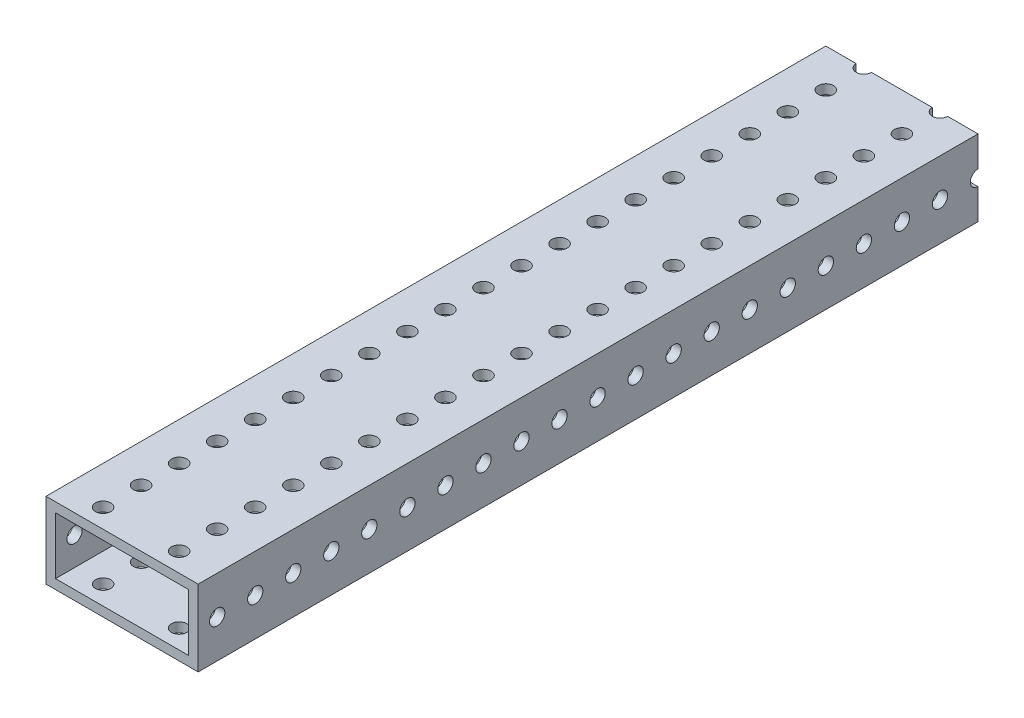
SolidWorks part; units mm, degrees
material "6061-T6 (SS)"
ref_plane "Front Plane" through (0, 0, 0) normal (0, 0, 1) x (1, 0, 0)
ref_plane "Top Plane" through (0, 0, 0) normal (0, 1, 0) x (1, 0, 0)
ref_plane "Right Plane" through (0, 0, 0) normal (1, 0, 0) x (0, 0, -1)
sketch "Sketch1" plane through (0, 0, 0) normal (0, 0, 1) x (1, 0, 0)
  line L0 (-22.225, 9.525) -> (22.225, 9.525)
  line L1 (-25.4, 12.7) -> (25.4, 12.7)
  line L2 (-25.4, 12.7) -> (-25.4, -12.7)
  line L3 (-25.4, -12.7) -> (25.4, -12.7)
  line L4 (25.4, 12.7) -> (25.4, -12.7)
  line L5 (22.225, 9.525) -> (22.225, -9.525)
  line L6 (-22.225, -9.525) -> (22.225, -9.525)
  line L7 (-22.225, 9.525) -> (-22.225, -9.525)
  line L8 (-25.4, 12.7) -> (25.4, -12.7) construction
  line L9 (25.4, 12.7) -> (-25.4, -12.7) construction
  point P5 (0, 0)
  dimension "D1" = 50.8
  dimension "D2" = 25.4
  dimension "D3" = 3.175
extrude "Boss-Extrude1" add sketch "Sketch1" along normal mid plane 368.3
sketch "Sketch5" plane through (-25.4, 0, 0) normal (-1, 0, 0) x (0, 0, 1)
  line L0 (184.15, -12.7) -> (-184.15, -12.7) construction
  line L1 (-184.15, 12.7) -> (-120.65, 12.7)
  line L2 (-184.15, 12.7) -> (-184.15, -12.7)
  line L3 (-184.15, -12.7) -> (-120.65, -12.7)
  line L4 (-120.65, 12.7) -> (-120.65, -12.7)
  dimension "D1" = 63.5
sketch "Sketch6" plane through (25.4, 0, 0) normal (1, 0, 0) x (0, 0, -1)
  line L0 (-184.15, -12.7) -> (-184.15, 12.7) construction
  line L1 (-184.15, 12.7) -> (184.15, 12.7) construction
  circle A0 centre (-177.8, 0) radius 2.5527
  circle A1 centre (-165.1, 0) radius 2.5527
  circle A2 centre (-152.4, 0) radius 2.5527
  circle A3 centre (-139.7, 0) radius 2.5527
  circle A4 centre (-127, 0) radius 2.5527
  circle A5 centre (-114.3, 0) radius 2.5527
  circle A6 centre (-101.6, 0) radius 2.5527
  circle A7 centre (-88.9, 0) radius 2.5527
  circle A8 centre (-76.2, 0) radius 2.5527
  circle A9 centre (-63.5, 0) radius 2.5527
  circle A10 centre (-50.8, 0) radius 2.5527
  circle A11 centre (-38.1, 0) radius 2.5527
  circle A12 centre (-25.4, 0) radius 2.5527
  circle A13 centre (-12.7, 0) radius 2.5527
  circle A14 centre (0, 0) radius 2.5527
  circle A15 centre (12.7, 0) radius 2.5527
  circle A16 centre (25.4, 0) radius 2.5527
  circle A17 centre (38.1, 0) radius 2.5527
  circle A18 centre (50.8, 0) radius 2.5527
  circle A19 centre (63.5, 0) radius 2.5527
  circle A20 centre (76.2, 0) radius 2.5527
  circle A21 centre (88.9, 0) radius 2.5527
  circle A22 centre (101.6, 0) radius 2.5527
  circle A23 centre (114.3, 0) radius 2.5527
  circle A24 centre (127, 0) radius 2.5527 construction
  circle A25 centre (139.7, 0) radius 2.5527 construction
  circle A26 centre (152.4, 0) radius 2.5527 construction
  circle A27 centre (165.1, 0) radius 2.5527 construction
  circle A28 centre (177.8, 0) radius 2.5527 construction
  dimension "D1" = 6.35
  dimension "D2" = 12.7
  dimension "D3" = 5.1054
  dimension "D4" = 29
extrude "Cut-Extrude5" cut sketch "Sketch6" against normal through all
extrude "Cut-Extrude6" cut sketch "Sketch5" against normal through all
sketch "Sketch2" plane through (0, 12.7, 0) normal (0, 1, 0) x (1, 0, 0)
  line L0 (25.4, -184.15) -> (-25.4, -184.15) construction
  line L1 (-25.4, -184.15) -> (-25.4, 120.65) construction
  line L4 (25.4, 184.15) -> (-25.4, 184.15) construction
  circle A0 centre (12.7, -177.8) radius 2.5527
  circle A1 centre (25.4, -171.45) radius 2.5527 construction
  circle A2 centre (-12.7, -177.8) radius 2.5527
  circle A3 centre (-12.7, -165.1) radius 2.5527
  circle A4 centre (12.7, -165.1) radius 2.5527 construction
  circle A5 centre (25.4, -158.75) radius 2.5527 construction
  circle A6 centre (-12.7, -152.4) radius 2.5527
  circle A7 centre (12.7, -152.4) radius 2.5527 construction
  circle A8 centre (25.4, -146.05) radius 2.5527 construction
  circle A9 centre (-12.7, -139.7) radius 2.5527
  circle A10 centre (12.7, -139.7) radius 2.5527 construction
  circle A11 centre (25.4, -133.35) radius 2.5527 construction
  circle A12 centre (-12.7, -127) radius 2.5527
  circle A13 centre (12.7, -127) radius 2.5527 construction
  circle A14 centre (25.4, -120.65) radius 2.5527 construction
  circle A15 centre (-12.7, -114.3) radius 2.5527
  circle A16 centre (12.7, -114.3) radius 2.5527 construction
  circle A17 centre (25.4, -107.95) radius 2.5527 construction
  circle A18 centre (-12.7, -101.6) radius 2.5527
  circle A19 centre (12.7, -101.6) radius 2.5527 construction
  circle A20 centre (25.4, -95.25) radius 2.5527 construction
  circle A21 centre (-12.7, -88.9) radius 2.5527
  circle A22 centre (12.7, -88.9) radius 2.5527 construction
  circle A23 centre (25.4, -82.55) radius 2.5527 construction
  circle A24 centre (-12.7, -76.2) radius 2.5527
  circle A25 centre (12.7, -76.2) radius 2.5527 construction
  circle A26 centre (25.4, -69.85) radius 2.5527 construction
  circle A27 centre (-12.7, -63.5) radius 2.5527
  circle A28 centre (12.7, -63.5) radius 2.5527 construction
  circle A29 centre (25.4, -57.15) radius 2.5527 construction
  circle A30 centre (-12.7, -50.8) radius 2.5527
  circle A31 centre (12.7, -50.8) radius 2.5527 construction
  circle A32 centre (25.4, -44.45) radius 2.5527 construction
  circle A33 centre (-12.7, -38.1) radius 2.5527
  circle A34 centre (12.7, -38.1) radius 2.5527 construction
  circle A35 centre (25.4, -31.75) radius 2.5527 construction
  circle A36 centre (-12.7, -25.4) radius 2.5527
  circle A37 centre (12.7, -25.4) radius 2.5527 construction
  circle A38 centre (25.4, -19.05) radius 2.5527 construction
  circle A39 centre (-12.7, -12.7) radius 2.5527
  circle A40 centre (12.7, -12.7) radius 2.5527 construction
  circle A41 centre (25.4, -6.35) radius 2.5527 construction
  circle A42 centre (-12.7, 0) radius 2.5527
  circle A43 centre (12.7, 0) radius 2.5527 construction
  circle A44 centre (25.4, 6.35) radius 2.5527 construction
  circle A45 centre (-12.7, 12.7) radius 2.5527
  circle A46 centre (12.7, 12.7) radius 2.5527 construction
  circle A47 centre (25.4, 19.05) radius 2.5527 construction
  circle A48 centre (-12.7, 25.4) radius 2.5527
  circle A49 centre (12.7, 25.4) radius 2.5527 construction
  circle A50 centre (25.4, 31.75) radius 2.5527 construction
  circle A51 centre (-12.7, 38.1) radius 2.5527
  circle A52 centre (12.7, 38.1) radius 2.5527 construction
  circle A53 centre (25.4, 44.45) radius 2.5527 construction
  circle A54 centre (-12.7, 50.8) radius 2.5527
  circle A55 centre (12.7, 50.8) radius 2.5527 construction
  circle A56 centre (25.4, 57.15) radius 2.5527 construction
  circle A57 centre (-12.7, 63.5) radius 2.5527
  circle A58 centre (12.7, 63.5) radius 2.5527 construction
  circle A59 centre (25.4, 69.85) radius 2.5527 construction
  circle A60 centre (-12.7, 76.2) radius 2.5527
  circle A61 centre (12.7, 76.2) radius 2.5527 construction
  circle A62 centre (25.4, 82.55) radius 2.5527 construction
  circle A63 centre (-12.7, 88.9) radius 2.5527
  circle A64 centre (12.7, 88.9) radius 2.5527 construction
  circle A65 centre (25.4, 95.25) radius 2.5527 construction
  circle A66 centre (-12.7, 101.6) radius 2.5527
  circle A67 centre (12.7, 101.6) radius 2.5527 construction
  circle A68 centre (25.4, 107.95) radius 2.5527 construction
  circle A69 centre (-12.7, 114.3) radius 2.5527 construction
  circle A70 centre (12.7, 114.3) radius 2.5527 construction
  circle A71 centre (25.4, 120.65) radius 2.5527 construction
  circle A72 centre (-12.7, 127) radius 2.5527 construction
  circle A73 centre (12.7, 127) radius 2.5527 construction
  circle A74 centre (25.4, 133.35) radius 2.5527 construction
  circle A75 centre (-12.7, 139.7) radius 2.5527
  circle A76 centre (12.7, 139.7) radius 2.5527 construction
  circle A77 centre (25.4, 146.05) radius 2.5527 construction
  circle A78 centre (-12.7, 152.4) radius 2.5527
  circle A79 centre (12.7, 152.4) radius 2.5527 construction
  circle A80 centre (25.4, 158.75) radius 2.5527 construction
  circle A81 centre (-12.7, 165.1) radius 2.5527
  circle A82 centre (12.7, 165.1) radius 2.5527 construction
  circle A83 centre (25.4, 171.45) radius 2.5527 construction
  circle A84 centre (-12.7, 177.8) radius 2.5527 construction
  circle A85 centre (12.7, 177.8) radius 2.5527 construction
  circle A86 centre (25.4, 184.15) radius 2.5527 construction
  circle A87 centre (-12.7, 190.5) radius 2.5527
  circle A88 centre (12.7, 190.5) radius 2.5527 construction
  circle A89 centre (25.4, 196.85) radius 2.5527 construction
  circle A90 centre (-12.7, 203.2) radius 2.5527
  circle A91 centre (12.7, 203.2) radius 2.5527 construction
  circle A92 centre (25.4, 209.55) radius 2.5527 construction
  circle A93 centre (-12.7, 215.9) radius 2.5527
  circle A94 centre (12.7, 215.9) radius 2.5527 construction
  circle A95 centre (25.4, 222.25) radius 2.5527 construction
  circle A96 centre (-12.7, 228.6) radius 2.5527
  circle A97 centre (12.7, 228.6) radius 2.5527 construction
  circle A98 centre (25.4, 234.95) radius 2.5527 construction
  circle A99 centre (-12.7, 241.3) radius 2.5527
  circle A100 centre (12.7, 241.3) radius 2.5527 construction
  circle A101 centre (25.4, 247.65) radius 2.5527 construction
  circle A108 centre (-12.7, 266.7) radius 2.5527 [skipped]
  circle A109 centre (12.7, 266.7) radius 2.5527 [skipped]
  circle A110 centre (25.4, 273.05) radius 2.5527 [skipped]
  circle A111 centre (-12.7, 254) radius 2.5527 [skipped]
  circle A112 centre (12.7, 254) radius 2.5527 [skipped]
  circle A113 centre (25.4, 260.35) radius 2.5527 [skipped]
  circle A114 centre (25.4, 260.35) radius 2.5527 construction
  circle A115 centre (12.7, 254) radius 2.5527 construction
  circle A116 centre (-12.7, 254) radius 2.5527
  circle A117 centre (25.4, 273.05) radius 2.5527 construction
  circle A118 centre (12.7, 266.7) radius 2.5527 construction
  circle A119 centre (-12.7, 266.7) radius 2.5527
  circle A120 centre (25.4, 285.75) radius 2.5527 construction
  circle A121 centre (12.7, 279.4) radius 2.5527 construction
  circle A122 centre (-12.7, 279.4) radius 2.5527
  circle A123 centre (25.4, 298.45) radius 2.5527 construction
  circle A124 centre (12.7, 292.1) radius 2.5527 construction
  circle A125 centre (-12.7, 292.1) radius 2.5527
  circle A126 centre (25.4, 311.15) radius 2.5527 construction
  circle A127 centre (12.7, 304.8) radius 2.5527 construction
  circle A128 centre (-12.7, 304.8) radius 2.5527
  circle A129 centre (25.4, 323.85) radius 2.5527 construction
  circle A130 centre (12.7, 317.5) radius 2.5527 construction
  circle A131 centre (-12.7, 317.5) radius 2.5527
  circle A132 centre (25.4, 336.55) radius 2.5527 construction
  circle A133 centre (12.7, 330.2) radius 2.5527 construction
  circle A134 centre (-12.7, 330.2) radius 2.5527
  circle A135 centre (25.4, 349.25) radius 2.5527 construction
  circle A136 centre (12.7, 342.9) radius 2.5527 construction
  circle A137 centre (-12.7, 342.9) radius 2.5527
  circle A138 centre (25.4, 361.95) radius 2.5527 construction
  circle A139 centre (12.7, 355.6) radius 2.5527 construction
  circle A140 centre (-12.7, 355.6) radius 2.5527
  circle A141 centre (25.4, 374.65) radius 2.5527 construction
  circle A142 centre (12.7, 368.3) radius 2.5527 construction
  circle A143 centre (-12.7, 368.3) radius 2.5527
  circle A144 centre (25.4, 387.35) radius 2.5527 construction
  circle A145 centre (12.7, 381) radius 2.5527 construction
  circle A146 centre (-12.7, 381) radius 2.5527
  circle A147 centre (25.4, 400.05) radius 2.5527 construction
  circle A148 centre (12.7, 393.7) radius 2.5527 construction
  circle A149 centre (-12.7, 393.7) radius 2.5527
  circle A150 centre (25.4, 412.75) radius 2.5527 construction
  circle A151 centre (12.7, 406.4) radius 2.5527 construction
  circle A152 centre (-12.7, 406.4) radius 2.5527
  circle A153 centre (12.7, -165.1) radius 2.5527
  circle A154 centre (12.7, -152.4) radius 2.5527
  circle A155 centre (12.7, -139.7) radius 2.5527
  circle A156 centre (12.7, -127) radius 2.5527
  circle A157 centre (12.7, -114.3) radius 2.5527
  circle A158 centre (12.7, -101.6) radius 2.5527
  circle A159 centre (12.7, -88.9) radius 2.5527
  circle A160 centre (12.7, -76.2) radius 2.5527
  circle A161 centre (12.7, -63.5) radius 2.5527
  circle A162 centre (12.7, -50.8) radius 2.5527
  circle A163 centre (12.7, -38.1) radius 2.5527
  circle A164 centre (12.7, -25.4) radius 2.5527
  circle A165 centre (12.7, -12.7) radius 2.5527
  circle A166 centre (12.7, 0) radius 2.5527
  circle A167 centre (12.7, 12.7) radius 2.5527
  circle A168 centre (12.7, 25.4) radius 2.5527
  circle A169 centre (12.7, 38.1) radius 2.5527
  circle A170 centre (12.7, 50.8) radius 2.5527
  circle A171 centre (12.7, 63.5) radius 2.5527
  circle A172 centre (12.7, 76.2) radius 2.5527
  circle A173 centre (12.7, 88.9) radius 2.5527
  circle A174 centre (12.7, 101.6) radius 2.5527
  circle A175 centre (12.7, 114.3) radius 2.5527 construction
  circle A176 centre (12.7, 127) radius 2.5527 construction
  circle A177 centre (12.7, 139.7) radius 2.5527
  circle A178 centre (12.7, 152.4) radius 2.5527
  circle A179 centre (12.7, 165.1) radius 2.5527
  circle A180 centre (12.7, 177.8) radius 2.5527 construction
  circle A181 centre (12.7, 190.5) radius 2.5527
  circle A182 centre (12.7, 203.2) radius 2.5527
  circle A183 centre (12.7, 215.9) radius 2.5527
  circle A184 centre (12.7, 228.6) radius 2.5527
  circle A185 centre (12.7, 241.3) radius 2.5527
  circle A186 centre (12.7, 254) radius 2.5527
  circle A187 centre (12.7, 266.7) radius 2.5527
  circle A188 centre (12.7, 279.4) radius 2.5527
  circle A189 centre (12.7, 292.1) radius 2.5527
  circle A190 centre (12.7, 304.8) radius 2.5527
  circle A191 centre (12.7, 317.5) radius 2.5527
  circle A192 centre (12.7, 330.2) radius 2.5527
  circle A193 centre (12.7, 342.9) radius 2.5527
  circle A194 centre (12.7, 355.6) radius 2.5527
  circle A195 centre (12.7, 368.3) radius 2.5527
  circle A196 centre (12.7, 381) radius 2.5527
  circle A197 centre (12.7, 393.7) radius 2.5527
  circle A198 centre (12.7, 406.4) radius 2.5527
  circle A199 centre (12.7, 419.1) radius 2.5527
  circle A200 centre (12.7, 431.8) radius 2.5527
  circle A201 centre (12.7, 444.5) radius 2.5527
  dimension "D2" = 5.1054
  dimension "D4" = 50
  dimension "D9" = 12.7
  dimension "D10" = 12.7
  dimension "D11" = 6.35
  dimension "D1" = 6.35
  dimension "D3" = 38.1
  dimension "D6" = 12.7
  dimension "D7" = 57.15
  dimension "D5" = 36
  dimension "D8" = 14
extrude "Cut-Extrude1" cut sketch "Sketch2" against normal through all
sketch "Sketch7" plane through (-25.4, 0, 0) normal (-1, 0, 0) x (0, 0, 1)
  line L5 (-120.65, 12.7) -> (-76.2, 12.7)
  line L6 (-120.65, 12.7) -> (-120.65, -12.7)
  line L7 (-120.65, -12.7) -> (-76.2, -12.7)
  line L8 (-76.2, 12.7) -> (-76.2, -12.7)
  point P0 (0, 0)
  dimension "D1" = 44.45
extrude "Cut-Extrude7" cut sketch "Sketch7" against normal through all
